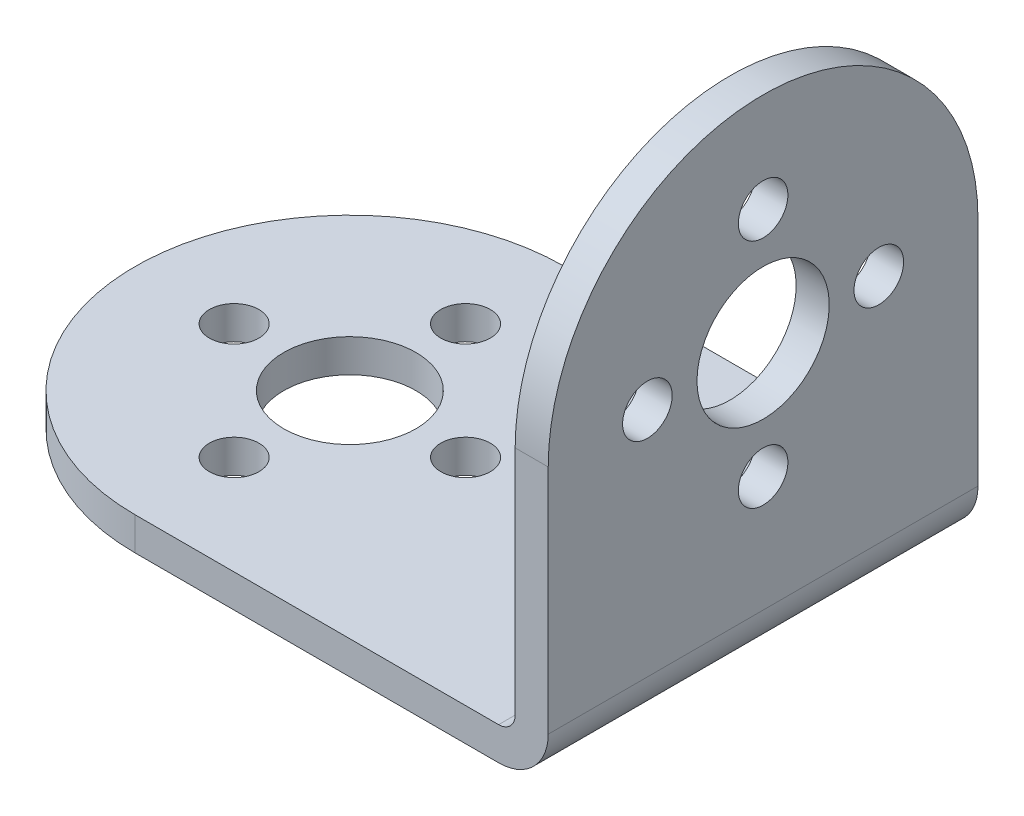
SolidWorks part; units mm, degrees
ref_plane "前视基准面" through (0, 0, 0) normal (0, 0, 1) x (1, 0, 0)
ref_plane "上视基准面" through (0, 0, 0) normal (0, 1, 0) x (1, 0, 0)
ref_plane "右视基准面" through (0, 0, 0) normal (1, 0, 0) x (0, 0, -1)
sketch "草图1" plane through (0, 0, 0) normal (0, 0, 1) x (1, 0, 0)
  line L1 (-19, -15) -> (19, -15)
  line L2 (-19, -15) -> (-19, -13)
  line L3 (17, 15) -> (19, 15)
  line L4 (19, -15) -> (19, 15)
  line L8 (17, -13) -> (17, 15)
  line L9 (17, -13) -> (-19, -13)
  point P0 (0, 0)
extrude "凸台-拉伸1" add sketch "草图1" along normal blind 26
fillet "圆角1" radius 1 1 edges at (17, -13, 13)
fillet "圆角2" radius 3 1 edges at (19, -15, 13)
sketch "草图2" plane through (17, 0, 0) normal (-1, 0, 0) x (0, 0, 1)
  line L1 (0, 2) -> (0, 15)
  line L2 (0, 15) -> (26, 15)
  line L3 (26, 15) -> (26, -12) construction
  line L4 (26, 15) -> (0, 15) construction
  line L5 (26, 15) -> (26, 2)
  arc A1 (26, 2) -> (0, 2) centre (13, 2) ccw
  circle A2 centre (13, 2) radius 4
  circle A4 centre (13, 9) radius 1.5
  circle A5 centre (20, 2) radius 1.5
  circle A6 centre (13, -5) radius 1.5
  circle A7 centre (6, 2) radius 1.5
  point P23 (13, 2)
  line M9 (0, 15) -> (0, -12)
  line M11 (26, -12) -> (26, 15)
  line M12 (26, 15) -> (0, 15)
  dimension "D1" = 4
extrude "切除-拉伸1" cut sketch "草图2" against normal blind 26 contours A1 M11 M12 | A1 L2 M9 | A7 | A4 | A6 | A5 | A2 region at (17, 12.0962, 23.0962) region at (17, 12.0962, 2.9038) region at (17, 2, 13) region at (17, 9, 13) region at (17, 2, 20) region at (17, -5, 13) region at (17, 2, 6)
sketch "草图3" plane through (0, -13, 0) normal (0, 1, 0) x (1, 0, 0)
  line L1 (-6, 0) -> (-19, 0)
  line L2 (-19, 0) -> (-19, -26)
  line L3 (-19, -26) -> (-6, -26)
  arc A1 (-6, 0) -> (-6, -26) centre (-6, -13) ccw
  circle A2 centre (-6, -13) radius 4
  circle A4 centre (-13, -13) radius 1.5
  circle A5 centre (-6, -6) radius 1.5
  circle A6 centre (1, -13) radius 1.5
  circle A7 centre (-6, -20) radius 1.5
  point P15 (-6, -13)
  line M6 (-19, -26) -> (16, -26)
  line M8 (16, 0) -> (-19, 0)
  line M9 (-19, 0) -> (-19, -26)
  dimension "D1" = 4
extrude "切除-拉伸2" cut sketch "草图3" against normal blind 26 contours A1 M8 M9 | A5 | A2 | A6 | A4 | A7 | A1 L2 M6 region at (-16.0962, -13, 2.9038) region at (-16.0962, -13, 23.0962) region at (-6, -13, 13) region at (-13, -13, 13) region at (-6, -13, 6) region at (1, -13, 13) region at (-6, -13, 20)
